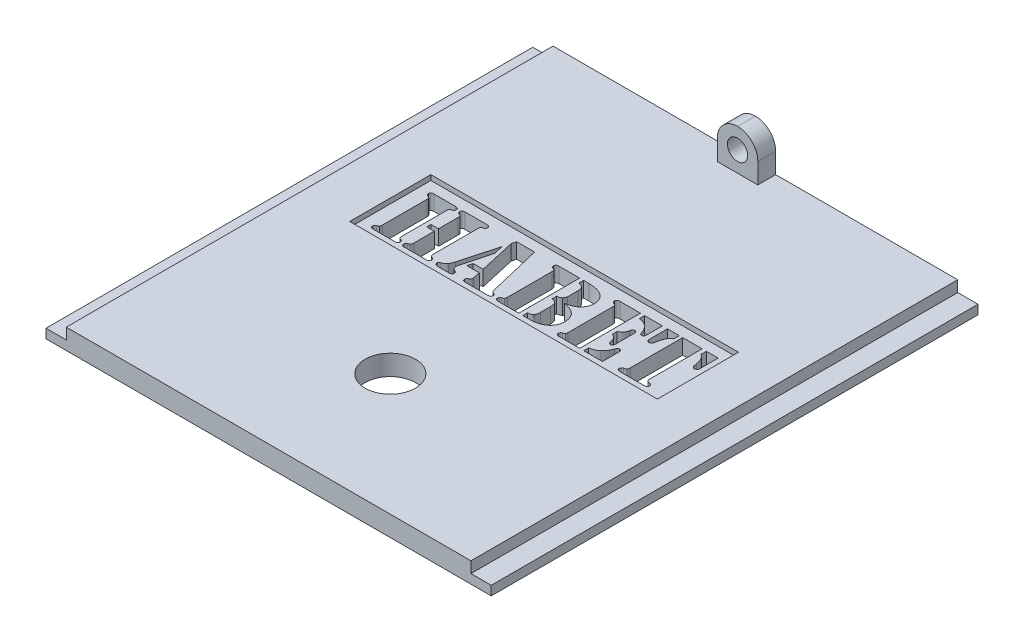
SolidWorks part; units mm, degrees
ref_plane "Front Plane" through (0, 0, 0) normal (0, 0, 1) x (1, 0, 0)
ref_plane "Top Plane" through (0, 0, 0) normal (0, 1, 0) x (1, 0, 0)
ref_plane "Right Plane" through (0, 0, 0) normal (1, 0, 0) x (0, 0, -1)
sketch "Sketch1" plane through (0, 0, 0) normal (0, 1, 0) x (1, 0, 0)
  line L1 (0, 0) -> (139.4003, 0)
  line L2 (0, 0) -> (0, 152.4)
  line L3 (0, 152.4) -> (139.4003, 152.4)
  line L4 (139.4003, 0) -> (139.4003, 152.4)
  dimension "D1" = 152.4
  dimension "D2" = 139.4003
extrude "Boss-Extrude1" add sketch "Sketch1" along normal blind 6.35
sketch "Sketch2" plane through (0, 6.35, 0) normal (0, 1, 0) x (1, 0, 0)
  line L0 (0, 0) -> (139.4003, 0) construction
  line L1 (0, 152.4) -> (6.35, 152.4)
  line L2 (0, 152.4) -> (0, 0)
  line L3 (0, 0) -> (6.35, 0)
  line L4 (6.35, 152.4) -> (6.35, 0)
  line L6 (139.4003, 152.4) -> (133.0503, 152.4)
  line L7 (139.4003, 152.4) -> (139.4003, 0)
  line L8 (139.4003, 0) -> (133.0503, 0)
  line L9 (133.0503, 152.4) -> (133.0503, 0)
  dimension "D1" = 6.35
  dimension "D2" = 6.35
extrude "Cut-Extrude1" cut sketch "Sketch2" against normal blind 3.4747
sketch "Sketch3" plane through (0, 6.35, 0) normal (0, 1, 0) x (1, 0, 0)
  line L0 (133.0503, 152.4) -> (6.35, 152.4) construction
  line L1 (63.3501, 152.4) -> (76.0501, 152.4)
  line L2 (63.3501, 152.4) -> (63.3501, 146.8137)
  line L3 (63.3501, 146.8137) -> (76.0501, 146.8137)
  line L4 (76.0501, 152.4) -> (76.0501, 146.8137)
  point P6 (69.7001, 152.4)
  point P7 (69.7001, 152.4)
  dimension "D1" = 12.7
extrude "Boss-Extrude2" add sketch "Sketch3" along normal blind 12.7
fillet "Fillet1" radius 6.35 2 edges at (63.3501, 19.05, -149.6068) (76.0501, 19.05, -149.6068)
sketch "Sketch4" plane through (0, 0, -152.4) normal (0, 0, -1) x (-1, 0, 0)
  circle A0 centre (-69.7001, 12.7) radius 3.175
  arc A1 (-63.3501, 12.7) -> (-69.7001, 19.05) centre (-69.7001, 12.7) ccw construction
  dimension "D1" = 3.175
extrude "Cut-Extrude2" cut sketch "Sketch4" against normal blind 6.35
sketch "Sketch7" plane through (0, 6.35, 0) normal (0, 1, 0) x (1, 0, 0)
  line L0 (6.35, 76.2) -> (133.0503, 76.2) construction
  line L3 (6.35, 0) -> (6.35, 152.4) construction
  line L4 (133.0503, 152.4) -> (133.0503, 0) construction
  text T0 "HABET" font "Stencil" height 19.05
extrude "Cut-Extrude7" cut sketch "Sketch7" against normal blind 6.35
sketch "Sketch9" plane through (0, 6.35, 0) normal (0, 1, 0) x (1, 0, 0)
  line L0 (35.9699, 95.25) -> (42.8243, 95.25) construction
  line L1 (22.0751, 98.425) -> (118.3835, 98.425)
  line L2 (22.0751, 98.425) -> (22.0751, 73.025)
  line L3 (22.0751, 73.025) -> (118.3835, 73.025)
  line L4 (118.3835, 98.425) -> (118.3835, 73.025)
  line L5 (42.8243, 76.2) -> (35.941, 76.2) construction
  line L6 (115.2085, 95.25) -> (115.2085, 89.5036) construction
  point P7 (39.3971, 95.25)
  point P10 (39.3826, 76.2)
  dimension "D1" = 3.175
  dimension "D2" = 3.175
  dimension "D3" = 3.175
  dimension "D4" = 3.175
extrude "Cut-Extrude8" cut sketch "Sketch9" against normal blind 1.5875
sketch "Sketch10" plane through (0, 6.35, 0) normal (0, 1, 0) x (1, 0, 0)
  line L0 (6.35, 0) -> (133.0503, 0) construction
  circle A0 centre (69.7001, 38.1) radius 7.874
  point P5 (69.7001, 0)
  dimension "D1" = 15.748
  dimension "D2" = 38.1
extrude "Cut-Extrude9" cut sketch "Sketch10" against normal through all
sketch "Sketch11" plane through (0, 0, -152.4) normal (0, 0, -1) x (-1, 0, 0)
  line L2 (-76.0501, 12.7) -> (-76.0501, 6.35)
  line L3 (-76.0501, 6.35) -> (-63.3501, 6.35)
  line L4 (-63.3501, 12.7) -> (-63.3501, 6.35)
  arc A0 (-63.3501, 12.7) -> (-76.0501, 12.7) centre (-69.7001, 12.7) ccw
  circle A1 centre (-69.7001, 12.7) radius 3.175
  dimension "D1" = 6.35
  dimension "D2" = 6.35
  dimension "D3" = 12.7
  dimension "D4" = 6.35
